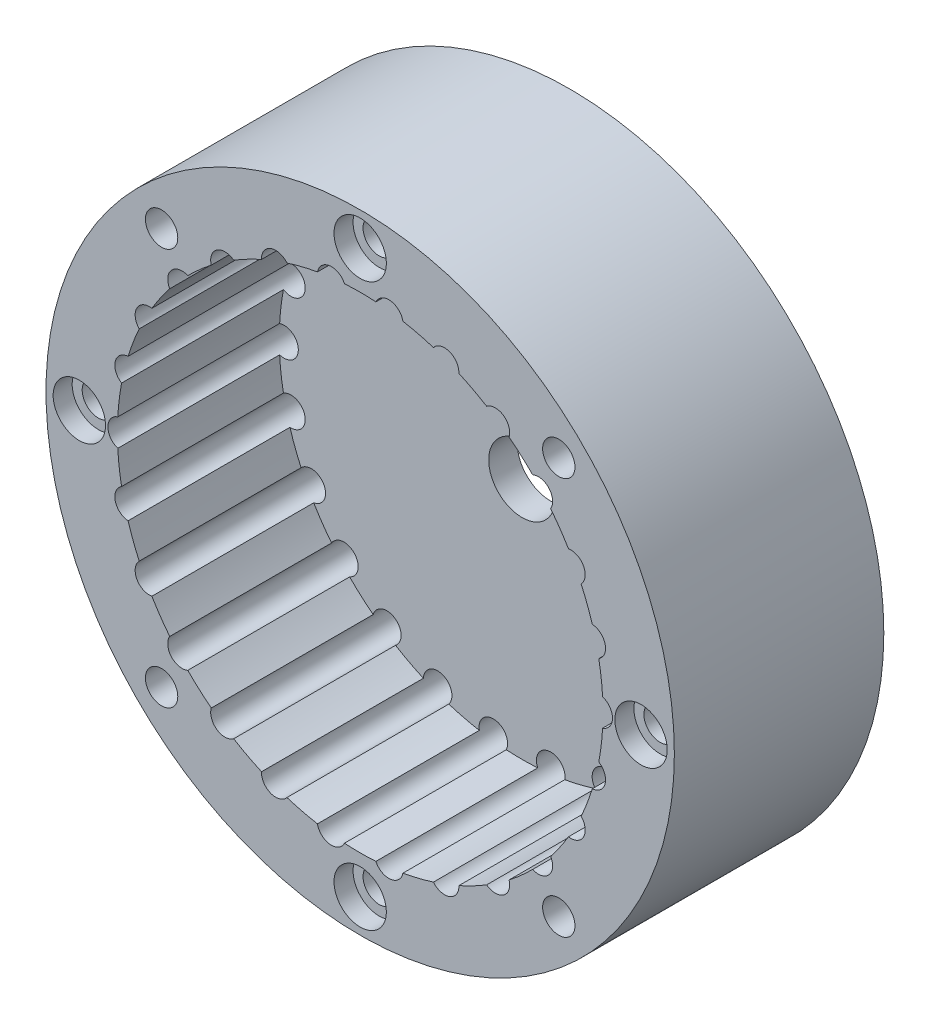
SolidWorks part; units mm, degrees
ref_plane "Front Plane" through (0, 0, 0) normal (0, 0, 1) x (1, 0, 0)
ref_plane "Top Plane" through (0, 0, 0) normal (0, 1, 0) x (1, 0, 0)
ref_plane "Right Plane" through (0, 0, 0) normal (1, 0, 0) x (0, 0, -1)
sketch "Sketch1" plane through (0, 0, 0) normal (0, 0, 1) x (1, 0, 0)
  line L0 (-25, 0) -> (25, 0) construction
  circle A0 centre (0, 0) radius 33
  circle A1 centre (0, 0) radius 25.5
  circle A2 centre (25, 0) radius 1.5
  circle A3 centre (24.2735, -5.9829) radius 1.5
  circle A4 centre (22.1364, -11.6181) radius 1.5
  circle A5 centre (18.7128, -16.5781) radius 1.5
  circle A6 centre (14.2016, -20.5746) radius 1.5
  circle A7 centre (8.8651, -23.3754) radius 1.5
  circle A8 centre (3.0134, -24.8177) radius 1.5
  circle A9 centre (-3.0134, -24.8177) radius 1.5
  circle A10 centre (-8.8651, -23.3754) radius 1.5
  circle A11 centre (-14.2016, -20.5746) radius 1.5
  circle A12 centre (-18.7128, -16.5781) radius 1.5
  circle A13 centre (-22.1364, -11.6181) radius 1.5
  circle A14 centre (-24.2735, -5.9829) radius 1.5
  circle A15 centre (-25, 0) radius 1.5
  circle A16 centre (-24.2735, 5.9829) radius 1.5
  circle A17 centre (-22.1364, 11.6181) radius 1.5
  circle A18 centre (-18.7128, 16.5781) radius 1.5
  circle A19 centre (-14.2016, 20.5746) radius 1.5
  circle A20 centre (-8.8651, 23.3754) radius 1.5
  circle A21 centre (-3.0134, 24.8177) radius 1.5
  circle A22 centre (3.0134, 24.8177) radius 1.5
  circle A23 centre (8.8651, 23.3754) radius 1.5
  circle A24 centre (14.2016, 20.5746) radius 1.5
  circle A25 centre (18.7128, 16.5781) radius 1.5
  circle A26 centre (22.1364, 11.6181) radius 1.5
  circle A27 centre (24.2735, 5.9829) radius 1.5
  point P7 (0, 0)
  point P61 (0, 0)
  dimension "D1" = 66
  dimension "D2" = 51
  dimension "D4" = 3
  dimension "D3" = 50
  dimension "D5" = 26
extrude "Boss-Extrude2" add sketch "Sketch1" along normal blind 17 contours A0 A27 A1 A2 A3 A4 A5 A6 A7 A8 A9 A10 A11 A12 A13 A14 A15 A16 A17 A18 A19 A20 A21 A22 A23 A24 A25 | A1 A17 | A1 A18 | A1 A19 | A1 A20 | A1 A21 | A1 A22 | A1 A23 | A1 A24 | A1 A25 | A1 A26 | A1 A27 | A1 A2 | A1 A4 | A1 A5 | A1 A6 | A1 A7 | A1 A8 | A1 A9 | A1 A10 | A1 A11 | A1 A12 | A1 A13 | A1 A14 | A1 A15 | A1 A16 | A1 A3 region at (-32.0666, 0, 0) region at (25.9066, 0, 0) region at (25.1538, 6.1999, 0) region at (25.1538, -6.1999, 0) region at (22.9392, 12.0394, 0) region at (22.9392, -12.0394, 0) region at (19.3914, 17.1793, 0) region at (19.3914, -17.1793, 0) region at (14.7166, 21.3207, 0) region at (14.7166, -21.3207, 0) region at (9.1866, 24.2231, 0) region at (9.1866, -24.2231, 0) region at (3.1227, 25.7177, 0) region at (3.1227, -25.7177, 0) region at (-3.1227, 25.7177, 0) region at (-3.1227, -25.7177, 0) region at (-9.1866, 24.2231, 0) region at (-9.1866, -24.2231, 0) region at (-14.7166, 21.3207, 0) region at (-14.7166, -21.3207, 0) region at (-19.3914, 17.1793, 0) region at (-19.3914, -17.1793, 0) region at (-22.9392, 12.0394, 0) region at (-22.9392, -12.0394, 0) region at (-25.1538, 6.1999, 0) region at (-25.1538, -6.1999, 0) region at (-25.9066, 0, 0)
extrude "Boss-Extrude3" add sketch "Sketch1<3>" against normal blind 5 contours A15 L0 A2 A1 A27 A26 A25 A24 A23 A22 A21 A20 A19 A18 A17 A16 | L0 A15 A1 A14 A13 A12 A11 A10 A9 A8 A7 A6 A5 A4 A3 A2 | A0 A27 A1 A2 A3 A4 A5 A6 A7 A8 A9 A10 A11 A12 A13 A14 A15 A16 A17 A18 A19 A20 A21 A22 A23 A24 A25 | A9 | A10 | A11 | A12 | A13 | A14 | A15 | A16 | A17 | A18 | A19 | A20 | A21 | A22 | A23 | A24 | A25 | A26 | A27 | A2 | A3 | A4 | A5 | A6 | A7 | A8 region at (0, 10.4969, 0) region at (0, -10.4969, 0) region at (-32.0666, 0, 0)
sketch "Sketch1<3>" plane through (0, 0, 0) normal (0, 0, 1) x (1, 0, 0) same geometry as "Sketch1"
extrude "Cut-Extrude4" cut sketch "Sketch1<5>" against normal blind 3 and the other way through all contours A18 | A19 | A20 | A21 | A22 | A23 | A24 | A25 | A26 | A27 | A2 | A3 | A4 | A5 | A6 | A7 | A8 | A9 | A10 | A11 | A12 | A13 | A14 | A15 | A16 | A17
sketch "Sketch1<5>" plane through (0, 0, 0) normal (0, 0, 1) x (1, 0, 0) same geometry as "Sketch1"
sketch "Sketch3" plane through (0, 0, 0) normal (0, 0, 1) x (1, 0, 0)
  line L0 (0, 29.5) -> (0, 0) construction
  circle A0 centre (0, 29.5) radius 1.7
  circle A1 centre (29.5, 0) radius 1.7
  circle A2 centre (0, -29.5) radius 1.7
  circle A3 centre (-29.5, 0) radius 1.7
  circle A8 centre (0, 0) radius 3.5
  point P0 (0, 0)
  point P21 (0, 0)
  dimension "D3" = 4
  dimension "D4" = 7
  dimension "D1" = 29.5
  dimension "D2" = 3.4
extrude "Cut-Extrude6" cut sketch "Sketch3" against normal through all both and the other way through all
sketch "Sketch4" plane through (0, 0, -5) normal (0, 0, -1) x (-1, 0, 0)
  circle A0 centre (0, 0) radius 10
  dimension "D1" = 20
extrude "Cut-Extrude7" cut sketch "Sketch4" against normal blind 2
sketch "Sketch5" plane through (0, 0, 17) normal (0, 0, 1) x (1, 0, 0)
  line L0 (0, 29.5) -> (0, -29.5) construction
sketch "Sketch6" plane through (0, 0, 17) normal (0, 0, 1) x (1, 0, 0)
  line L1 (-20.8597, 20.8597) -> (0, 0) construction
  line L2 (0, 29.5) -> (0, -29.5) construction
  circle A0 centre (-20.8597, 20.8597) radius 1.7
  circle A1 centre (20.8597, 20.8597) radius 1.7
  circle A2 centre (20.8597, -20.8597) radius 1.7
  circle A3 centre (-20.8597, -20.8597) radius 1.7
  point P15 (0, 0)
  dimension "D1" = 3.4
  dimension "D2" = 29.5
  dimension "D3" = 45
  dimension "D4" = 4
extrude "Cut-Extrude8" cut sketch "Sketch6" against normal blind 10
sketch "Sketch7" plane through (0, 0, 17) normal (0, 0, 1) x (1, 0, 0)
  circle A0 centre (0, 29.5) radius 2.75
  circle A1 centre (29.5, 0) radius 2.75
  circle A2 centre (0, -29.5) radius 2.75
  circle A3 centre (-29.5, 0) radius 2.75
  point P12 (0, 0)
  dimension "D1" = 5.5
  dimension "D2" = 4
extrude "Cut-Extrude9" cut sketch "Sketch7" against normal blind 2
equation "\"N_pins\"= 26"
equation "\"N_lobes\"= \"N_pins\" - 1"
equation "\"R_pc\"= 25"
equation "\"D_pin\"= 3"
equation "\"R_pin\"= \"D_pin\" / 2"
equation "\"ecc\"= 0.72"
equation "\"t_disc\"= 7"
equation "\"N_out\"= 8"
equation "\"D_outc\"=22"
equation "\"D_roller\"= 5"
equation "\"D_outhole\"= \"D_roller\" + 2 * \"ecc\""
equation "\"D_cam_OD\"= 21"
equation "\"D_cam_ID\"= 10"
equation "\"clr_bore\"= 1"
equation "\"D_bore\"= 2 * \"R_pc\" + \"clr_bore\""
equation "\"t_wall\"= 7.5"
equation "\"D_housing\"= \"D_bore\" + 2 * \"t_wall\""
equation "\"D1@Sketch1\"=\"D_housing\""
equation "\"D2@Sketch1\"=\"D_bore\""
equation "\"D3@Sketch1\"=2 * \"R_pc\""
equation "\"D4@Sketch1\"=\"D_pin\""
equation "\"L_housing\"=17"
equation "\"D1@Boss-Extrude2\"=\"L_housing\""
